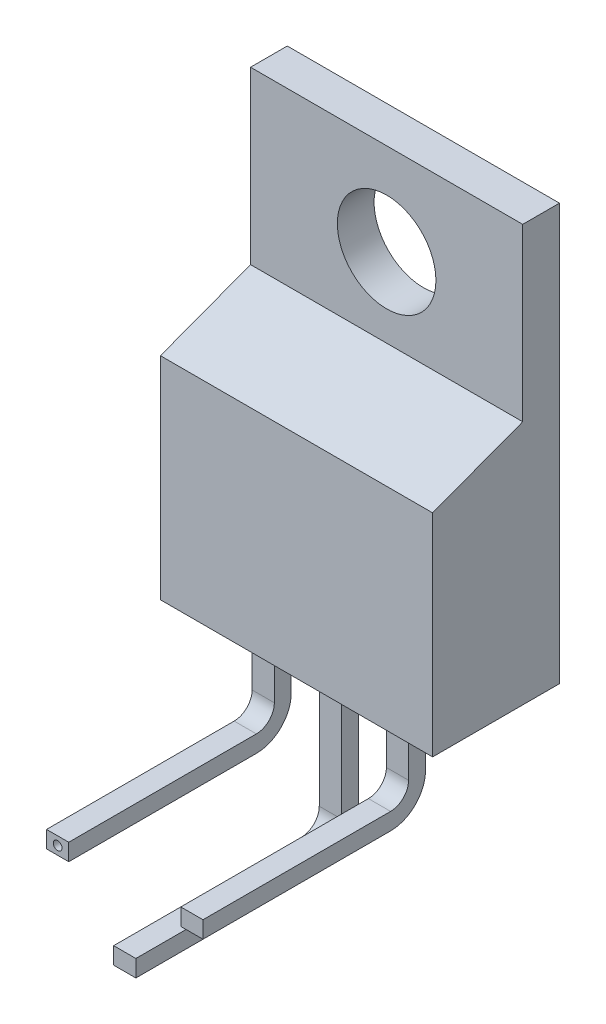
SolidWorks part; units mm, degrees
ref_plane "Front" through (0, 0, 0) normal (0, 0, 1) x (1, 0, 0)
ref_plane "Top" through (0, 0, 0) normal (0, 1, 0) x (1, 0, 0)
ref_plane "Right" through (0, 0, 0) normal (1, 0, 0) x (0, 0, -1)
sketch "Эскиз1" plane through (0, 0, 0) normal (0, 0, 1) x (1, 0, 0)
  line L1 (-1, -1) -> (1, -1)
  line L2 (-1, -1) -> (-1, 1)
  line L3 (-1, 1) -> (1, 1)
  line L4 (1, -1) -> (1, 1)
  line L5 (4.08, -1) -> (6.08, -1)
  line L6 (4.08, -1) -> (4.08, 1)
  line L7 (4.08, 1) -> (6.08, 1)
  line L8 (6.08, -1) -> (6.08, 1)
  line L9 (1.54, -2.5) -> (3.54, -2.5)
  line L10 (1.54, -2.5) -> (1.54, -0.5)
  line L11 (1.54, -0.5) -> (3.54, -0.5)
  line L12 (3.54, -2.5) -> (3.54, -0.5)
sketch "Эскиз3" plane through (0, 0, 0) normal (0, 0, 1) x (1, 0, 0)
  line L0 (-0.42, 0) -> (0.42, 0) construction
  line L1 (-0.42, 0.32) -> (0.42, 0.32)
  line L2 (-0.42, 0.32) -> (-0.42, -0.32)
  line L3 (-0.42, -0.32) -> (0.42, -0.32)
  line L4 (0.42, 0.32) -> (0.42, -0.32)
  line L5 (0, 0.32) -> (0, -0.32) construction
  line L6 (2.54, 1.6352) -> (2.54, -3.5178) construction
  line L8 (4.66, 0.32) -> (4.66, -0.32)
  line L9 (5.5, -0.32) -> (4.66, -0.32)
  line L10 (5.5, 0.32) -> (4.66, 0.32)
  line L11 (5.5, 0.32) -> (5.5, -0.32)
  dimension "D1" = 0.84
  dimension "D2" = 0.64
  dimension "D3" = 2.54
sketch "Эскиз4" plane through (0, 0, 0) normal (0, 0, 1) x (1, 0, 0)
  line L0 (2.12, -2.54) -> (2.96, -2.54) construction
  line L1 (2.12, -2.22) -> (2.96, -2.22)
  line L2 (2.12, -2.22) -> (2.12, -2.86)
  line L3 (2.12, -2.86) -> (2.96, -2.86)
  line L4 (2.96, -2.22) -> (2.96, -2.86)
  line L5 (2.54, -2.22) -> (2.54, -2.86) construction
  point P8 (2.54, -2.54)
  dimension "D1" = 0.84
  dimension "D2" = 0.64
  dimension "D3" = 2.54
  dimension "D4" = 2.54
ref_plane "Плоскость1" through (0, 3.5, 0) normal (0, 1, 0) x (-1, 0, 0)
sketch "Эскиз5" plane through (0, 3.5, 0) normal (0, 1, 0) x (-1, 0, 0)
  line L0 (-2.54, 0) -> (-2.54, -4.8) construction
  line L1 (2.61, 0) -> (-7.69, 0)
  line L3 (-7.69, 0) -> (-7.69, -4.8)
  line L5 (-9.4262, 0) -> (-8.0568, 0) construction
  line L6 (2.61, -4.8) -> (-7.69, -4.8)
  line L7 (2.61, 0) -> (2.61, -4.8)
  dimension "D1" = 4.8
  dimension "D2" = 10.3
  dimension "D3" = 2.54
sketch "Эскиз8" plane through (0, 0, 0) normal (1, 0, 0) x (0, 0, -1)
  line L1 (0, 0) -> (0.6, 0)
  line L3 (0, 3.1835) -> (0, 2.5724) construction
  line L4 (1.6, 1) -> (1.6, 3.5)
  arc A1 (0.6, 0) -> (1.6, 1) centre (0.6, 1) ccw
  point P12 (0, 0)
  dimension "D2" = 1.6
  dimension "D1" = 1
  dimension "D4" = 3.5
  dimension "D5" = 0.6
  dimension "D6" = 2.5
sketch "Эскиз9" plane through (0, 0, 0) normal (1, 0, 0) x (0, 0, -1)
  line L1 (0, -2.54) -> (0.6, -2.54)
  line L2 (0, -1.6929) -> (0, -2.6032) construction
  line L3 (0, 1.6352) -> (0, -3.5178) construction
  line L4 (1.6, -1.54) -> (1.6, 4.77)
  arc A1 (0.6, -2.54) -> (1.6, -1.54) centre (0.6, -1.54) ccw
  point P14 (0, -2.54)
  dimension "D2" = 1.6
  dimension "D4" = 0.6
  dimension "D3" = 1
  dimension "D1" = 2.54
  dimension "D5" = 6.31
  dimension "D6" = 7.31
extrude "Вытянуть1" add sketch "Эскиз5" along normal blind 15.75
sketch "Эскиз10" plane through (0, 0, 0) normal (1, 0, 0) x (0, 0, -1)
  line L0 (0, 19.25) -> (3.41, 19.25)
  line L2 (3.41, 19.25) -> (3.41, 12.78)
  line L3 (3.41, 12.78) -> (0, 11.5)
  line L5 (0, 11.5) -> (0, 19.25)
  dimension "D1" = 6.47
  dimension "D2" = 3.41
  dimension "D3" = 7.75
extrude "Вырез-Вытянуть1" cut sketch "Эскиз10" against normal up to surface and the other way up to surface up to face at (-2.61, 11.375, -2.4) other way up to face at (7.69, 11.375, -2.4)
sketch "Эскиз11" plane through (0, 0, 0) normal (0, 0, 1) x (1, 0, 0)
  circle A0 centre (2.54, 15.77) radius 1.865
  dimension "D3" = 3.73
extrude "Вырез-Вытянуть2" cut sketch "Эскиз11" against normal up to surface (4.8 mm away) up to face at (2.54, 11.375, -4.8)
sweep "По траектории1" add profiles "Эскиз3" path "Эскиз8"
sweep "По траектории2" add profiles "Эскиз4" path "Эскиз9"
extrude "Вытянуть2" add sketch "Эскиз3<3>" along normal blind 2.5
sketch "Эскиз3<3>" plane through (0, 0, 0) normal (0, 0, 1) x (1, 0, 0) same geometry as "Эскиз3"
extrude "Вытянуть3" add sketch "Эскиз4<3>" along normal blind 2.5
sketch "Эскиз4<3>" plane through (0, 0, 0) normal (0, 0, 1) x (1, 0, 0) same geometry as "Эскиз4"
sketch "Эскиз12" plane through (0, 0, 2.5) normal (0, 0, 1) x (1, 0, 0)
  line L4 (-0.42, 0.32) -> (-0.42, -0.32)
  line L5 (-0.42, -0.32) -> (0.42, -0.32)
  line L6 (0.42, -0.32) -> (0.42, 0.32)
  line L7 (0.42, 0.32) -> (-0.42, 0.32)
  line L8 (-0.42, 0.32) -> (-0.42, -0.32)
  line L9 (-0.42, -0.32) -> (0.42, -0.32)
  line L10 (0.42, -0.32) -> (0.42, 0.32)
  line L11 (0.42, 0.32) -> (-0.42, 0.32)
  line L12 (5.5, 0.32) -> (4.66, 0.32)
  line L13 (4.66, 0.32) -> (4.66, -0.32)
  line L14 (4.66, -0.32) -> (5.5, -0.32)
  line L15 (5.5, -0.32) -> (5.5, 0.32)
  line L16 (5.5, 0.32) -> (4.66, 0.32)
  line L17 (4.66, 0.32) -> (4.66, -0.32)
  line L18 (4.66, -0.32) -> (5.5, -0.32)
  line L19 (5.5, -0.32) -> (5.5, 0.32)
  line L20 (2.12, -2.22) -> (2.12, -2.86)
  line L21 (2.12, -2.86) -> (2.96, -2.86)
  line L22 (2.96, -2.86) -> (2.96, -2.22)
  line L23 (2.96, -2.22) -> (2.12, -2.22)
  line L24 (2.12, -2.22) -> (2.12, -2.86)
  line L25 (2.12, -2.86) -> (2.96, -2.86)
  line L26 (2.96, -2.86) -> (2.96, -2.22)
  line L27 (2.96, -2.22) -> (2.12, -2.22)
  dimension "D1" = 0
  dimension "D2" = 0
  dimension "D3" = 0
extrude "Вытянуть4" add sketch "Эскиз12" along normal blind 4
sketch "Эскиз13" plane through (0, 0, 6.5) normal (0, 0, 1) x (1, 0, 0)
  circle A0 centre (0, 0) radius 0.1652
extrude "Вырез-Вытянуть3" cut sketch "Эскиз13" against normal blind 1
